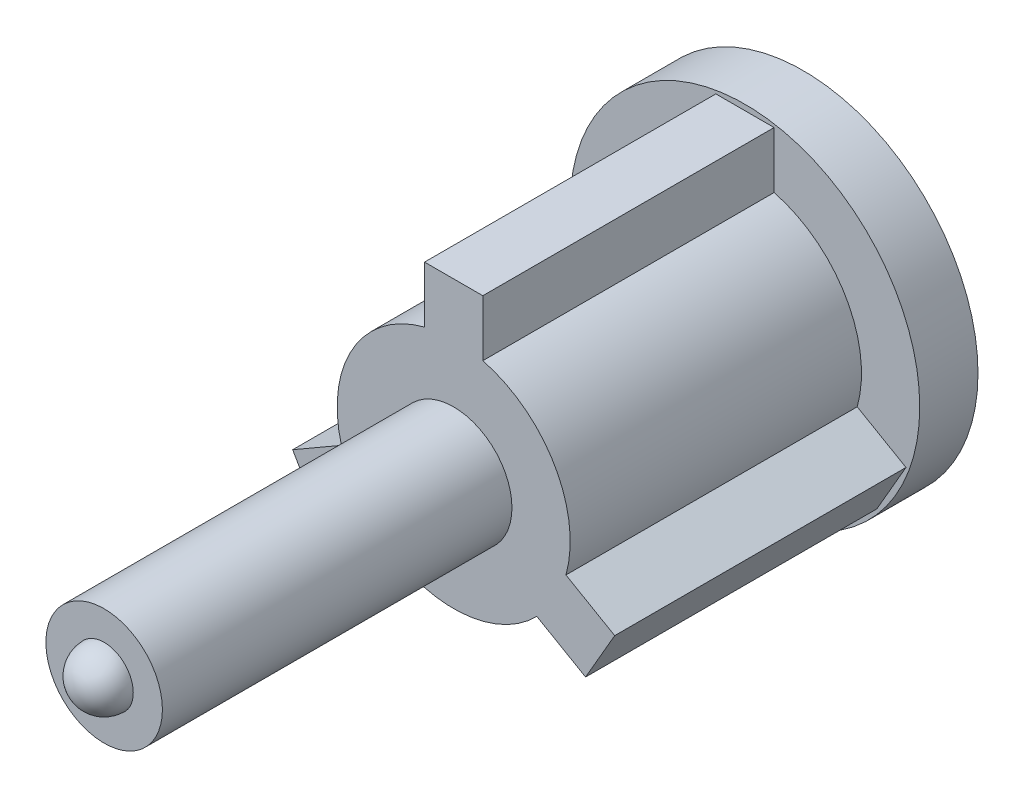
SolidWorks part; units mm, degrees
material "PE High Density"
ref_plane "Front" through (0, 0, 0) normal (0, 0, 1) x (1, 0, 0)
ref_plane "Top" through (0, 0, 0) normal (0, 1, 0) x (1, 0, 0)
ref_plane "Right" through (0, 0, 0) normal (1, 0, 0) x (0, 0, -1)
sketch "Sketch1" plane through (0, 0, 0) normal (0, 0, 1) x (1, 0, 0)
  circle A0 centre (0, 0) radius 3
extrude "Boss-Extrude1" add sketch "Sketch1" along normal blind 1
sketch "Sketch2" plane through (0, 0, 1) normal (0, 0, 1) x (1, 0, 0)
  circle A0 centre (0, 0) radius 2
extrude "Boss-Extrude2" add sketch "Sketch2" along normal blind 5
sketch "Sketch3" plane through (0, 0, 6) normal (0, 0, 1) x (1, 0, 0)
  circle A0 centre (0, 0) radius 1
extrude "Boss-Extrude3" add sketch "Sketch3" along normal blind 6
sketch "Sketch4" plane through (0, 0, 12) normal (0, 0, 1) x (1, 0, 0)
  circle A0 centre (0, 0) radius 0.5
extrude "Boss-Extrude4" add sketch "Sketch4" along normal blind 0.5
fillet "Fillet2" radius 0.5 1 edges at (0.5, 0, 12.5)
sketch "Sketch5" plane through (0, 0, 1) normal (0, 0, 1) x (1, 0, 0)
  line L1 (-0.5, 2.9027) -> (0.5, 2.9027)
  line L2 (-0.5, 2.9027) -> (-0.5, 0.9882)
  line L3 (-0.5, 0.9882) -> (0.5, 0.9882)
  line L4 (0.5, 2.9027) -> (0.5, 0.9882)
  line L5 (-0.5, 2.9027) -> (0.5, 0.9882) construction
  line L6 (-0.5, 0.9882) -> (0.5, 2.9027) construction
  point P0 (0, 1.9455)
extrude "Boss-Extrude5" add sketch "Sketch5" along normal blind 5
pattern_circular "CirPattern1" count 3 every 120 about axis through (0, 0, 6) along (0, 0, -1) of "Boss-Extrude5"
sketch "Sketch6" plane through (0, 0, 0) normal (0, 0, -1) x (-1, 0, 0)
  circle A0 centre (0, 0) radius 1.5
extrude "Cut-Extrude1" cut sketch "Sketch6" against normal blind 5
